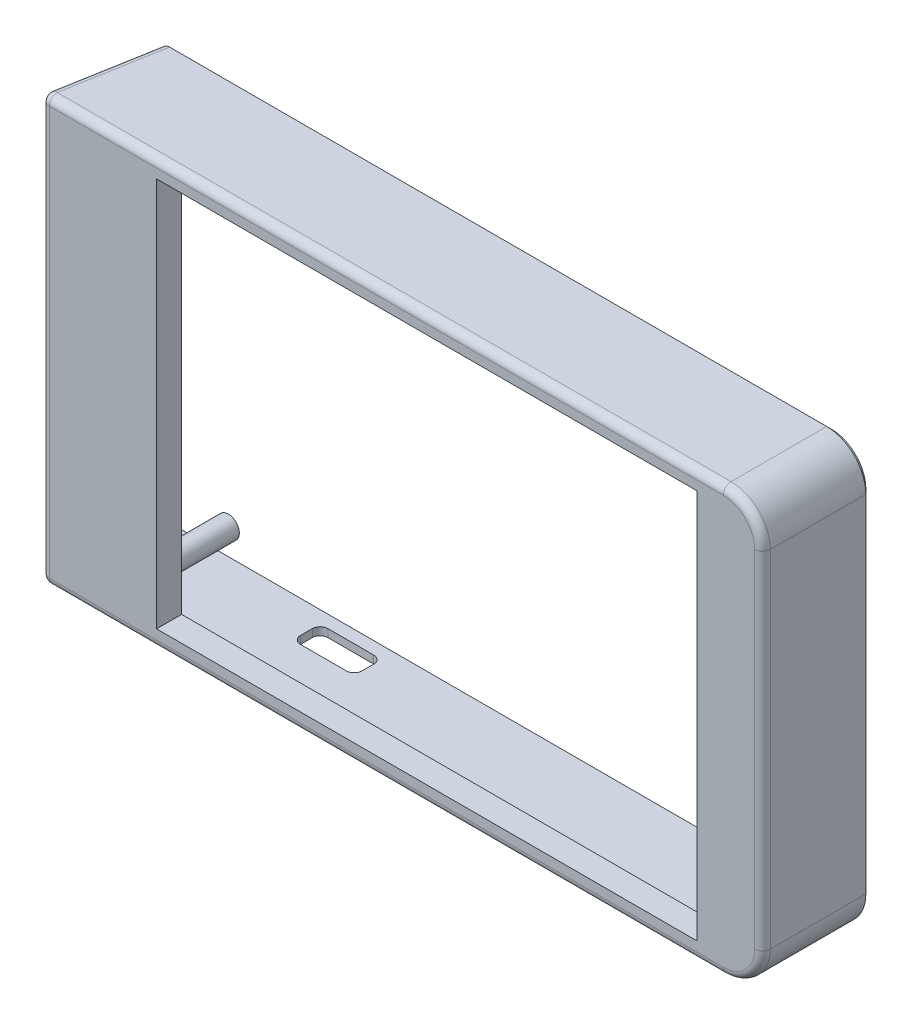
SolidWorks part; units mm, degrees
ref_plane "Front Plane" through (0, 0, 0) normal (0, 0, 1) x (1, 0, 0)
ref_plane "Top Plane" through (0, 0, 0) normal (0, 1, 0) x (1, 0, 0)
ref_plane "Right Plane" through (0, 0, 0) normal (1, 0, 0) x (0, 0, -1)
sketch "Sketch1" plane through (0, 0, 0) normal (0, 0, 1) x (1, 0, 0)
  line L0 (-39.8484, 30.2167) -> (-39.8484, 39.4369) construction
  line L1 (-52.5926, -12.5567) -> (37.3102, -12.5567)
  line L2 (-52.5926, -12.5567) -> (-52.5926, 41.6369)
  line L3 (-52.5926, 41.6369) -> (37.3102, 41.6369)
  line L4 (37.3102, -12.5567) -> (37.3102, 41.6369)
  line L5 (-40.0484, 39.6369) -> (29.1634, 39.6369)
  line L6 (-40.0484, 39.6369) -> (-40.0484, -10.5249)
  line L7 (-40.0484, -10.5249) -> (29.1634, -10.5249)
  line L8 (29.1634, 39.6369) -> (29.1634, -10.5249)
  line L9 (-39.8484, 39.4369) -> (29.1634, 39.4369) construction
  line L10 (29.1634, 39.4369) -> (29.1634, -10.5249) construction
  line L11 (29.1634, -10.5249) -> (-39.8484, -10.5249) construction
  line L13 (35.3102, -10.5567) -> (-50.5926, -10.5567) construction
  line L14 (-50.5926, -10.5567) -> (-50.5926, 39.5829) construction
  line L15 (35.3102, 39.5829) -> (35.3102, -10.5567) construction
  dimension "D1" = 2
  dimension "D2" = 2
  dimension "D3" = 0.2
  dimension "D4" = 0.2
  dimension "D5" = 0
  dimension "D6" = 0
  dimension "D7" = 2
  dimension "D8" = 2
extrude "Boss-Extrude1" add sketch "Sketch1" along normal blind 3.2
sketch "Sketch2" plane through (0, 0, 0) normal (0, 0, -1) x (-1, 0, 0)
  line L0 (49.6782, 29.2768) -> (49.6782, 27.6893) construction
  line L1 (50.6782, 33.2931) -> (46.1987, 33.2931)
  line L2 (50.6782, 33.2931) -> (50.6782, -2.2669)
  line L3 (50.6782, -2.2669) -> (46.1987, -2.2669)
  line L4 (46.1987, 33.2931) -> (46.1987, -2.2669)
  line L5 (47.1987, 31.9912) -> (47.1987, -2.9651) construction
  line L6 (47.6145, 32.2931) -> (49.202, 32.2931) construction
  line L7 (49.202, -3.2669) -> (47.6145, -3.2669) construction
  dimension "D1" = 1
  dimension "D2" = 1
  dimension "D3" = 1
  dimension "D4" = 1
extrude "Cut-Extrude1" cut sketch "Sketch2" against normal blind 2
sketch "Sketch3" plane through (0, 0, 0) normal (0, 0, -1) x (-1, 0, 0)
  line L1 (-37.3102, 41.6369) -> (52.5926, 41.6369)
  line L2 (-37.3102, 41.6369) -> (-37.3102, -12.5567)
  line L3 (-37.3102, -12.5567) -> (52.5926, -12.5567)
  line L4 (52.5926, 41.6369) -> (52.5926, -12.5567)
  line L5 (-36.3102, 40.6369) -> (51.5926, 40.6369)
  line L6 (-36.3102, 40.6369) -> (-36.3102, -11.5567)
  line L7 (-36.3102, -11.5567) -> (51.5926, -11.5567)
  line L8 (51.5926, 40.6369) -> (51.5926, -11.5567)
  dimension "D1" = 1
  dimension "D2" = 1
  dimension "D3" = 1
  dimension "D4" = 1
extrude "Boss-Extrude2" add sketch "Sketch3" along normal blind 10
sketch "Sketch4" plane through (0, 0, 0) normal (0, 0, -1) x (-1, 0, 0)
  line L0 (-35.3102, 14.5131) -> (49.6764, 14.5131) construction
  line L1 (-35.3102, 39.5829) -> (-35.3102, -10.5567) construction
  line L2 (49.6764, -2.9651) -> (49.6764, 31.9912) construction
  circle A0 centre (-32.2241, -7.4452) radius 1.4
  circle A2 centre (-32.2241, 36.4714) radius 1.4
  circle A3 centre (43.8743, -7.4452) radius 1.4
  circle A4 centre (43.8743, 36.4714) radius 1.4
  dimension "D1" = 2.8
extrude "Boss-Extrude3" add sketch "Sketch4" along normal offset from surface (9.8 mm away) 0.2
sketch "Sketch5" plane through (0, -12.5567, 0) normal (0, -1, 0) x (1, 0, 0)
  line L0 (-31.1676, -6) -> (-31.1676, -8.5) construction
  line L1 (-31.3676, -9) -> (-23.5176, -9)
  line L2 (-31.3676, -9) -> (-31.3676, -5.5)
  line L3 (-31.3676, -5.5) -> (-23.5176, -5.5)
  line L4 (-23.5176, -9) -> (-23.5176, -5.5)
  line L5 (-23.7176, -6) -> (-23.7176, -8.5) construction
  line L6 (-31.1676, -6) -> (-23.7176, -6) construction
  line L7 (-31.1676, -8.5) -> (-23.7176, -8.5) construction
  dimension "D1" = 0.2
  dimension "D2" = 0.2
  dimension "D3" = 0.5
  dimension "D4" = 0.5
extrude "Cut-Extrude2" cut sketch "Sketch5" against normal up to surface (1 mm away) up to face at (-7.6412, -11.5567, -5)
sketch "Sketch6" plane through (0, -12.5567, 0) normal (0, -1, 0) x (-1, 0, 0)
  line L0 (52.5926, 10) -> (54.9201, -3.2)
  line L1 (54.9201, -3.2) -> (52.5926, -3.2)
  line L2 (52.5926, -3.2) -> (52.5926, 10)
  line L3 (52.5926, -3.2) -> (-37.3102, -3.2) construction
  dimension "D1" = 80
extrude "Boss-Extrude4" add sketch "Sketch6" against normal up to surface (54.1936 mm away) up to face at (-7.6412, 41.6369, -3.4)
fillet "Fillet1" radius 4 2 edges at (36.3102, 40.6369, -5) (36.3102, -11.5567, -5)
fillet "Fillet2" radius 5 2 edges at (37.3102, -12.5567, -3.4) (37.3102, 41.6369, -3.4)
fillet "Fillet3" radius 1 5 edges at (-11.305, -12.5567, 3.2) (35.8457, -11.0923, 3.2) (37.3102, 14.5401, 3.2) (35.8457, 40.1724, 3.2) (-11.305, 41.6369, 3.2)
sketch "Sketch7" plane through (0, 0, -9.8) normal (0, 0, -1) x (-1, 0, 0)
  circle A0 centre (-32.2241, -7.4452) radius 0.7
  circle A1 centre (-32.2241, 36.4714) radius 0.7
  circle A2 centre (43.8743, 36.4714) radius 0.7
  circle A3 centre (43.8743, -7.4452) radius 0.7
  dimension "D1" = 1.4
extrude "Cut-Extrude3" cut sketch "Sketch7" against normal blind 6
fillet "Fillet4" radius 1 5 edges at (-53.6682, -12.5567, -3.9) (-54.8685, -12.2638, 2.9071) (-54.9201, 14.5401, 3.2) (-54.8685, 41.344, 2.9071) (-53.6682, 41.6369, -3.9)
fillet "Fillet5" radius 1 4 edges at (-31.3676, -12.0567, -5.5) (-31.3676, -12.0567, -9) (-23.5176, -12.0567, -9) (-23.5176, -12.0567, -5.5)
sketch "Sketch9" plane through (0, 0, -10) normal (0, 0, -1) x (-1, 0, 0)
  line L0 (-32.3102, 40.6369) -> (51.5926, 40.6369)
  line L1 (51.5926, 40.6369) -> (51.5926, -11.5567)
  line L2 (51.5926, -11.5567) -> (-32.3102, -11.5567)
  line L3 (-36.3102, 36.6369) -> (-36.3102, -7.5567)
  line L4 (51.9926, 41.0369) -> (-32.3102, 41.0369)
  line L5 (-36.7102, 36.6369) -> (-36.7102, -7.5567)
  line L6 (-32.3102, -11.9567) -> (51.9926, -11.9567)
  line L7 (51.9926, -11.9567) -> (51.9926, 41.0369)
  arc A0 (-36.3102, 36.6369) -> (-32.3102, 40.6369) centre (-32.3102, 36.6369) cw
  arc A1 (-36.3102, -7.5567) -> (-32.3102, -11.5567) centre (-32.3102, -7.5567) ccw
  arc A2 (-36.3102, -7.5567) -> (-32.3102, -11.5567) centre (-32.3102, -7.5567) ccw construction
  arc A3 (-32.3102, 40.6369) -> (-36.3102, 36.6369) centre (-32.3102, 36.6369) ccw construction
  arc A4 (-36.7102, 36.6369) -> (-32.3102, 41.0369) centre (-32.3102, 36.6369) cw
  arc A5 (-36.7102, -7.5567) -> (-32.3102, -11.9567) centre (-32.3102, -7.5567) ccw
  point P28 (-36.7102, -6.2766)
  dimension "D1" = 0.4
  dimension "D2" = 0.4
  dimension "D3" = 0.4
  dimension "D4" = 0.4
extrude "Boss-Extrude6" add sketch "Sketch9" along normal blind 0.6
fillet "Fillet6" radius 0.4 2 edges at (-51.9926, 41.0369, -10.3) (-51.9926, -11.9567, -10.3)
sketch "Sketch10" plane through (0, 0, 3.2) normal (0, 0, 1) x (1, 0, 0)
  line L0 (-40.0484, -10.3249) -> (-40.0484, -10.5249)
  line L1 (-40.0484, 39.6369) -> (29.1634, 39.6369)
  line L2 (-40.0484, 39.6369) -> (-40.0484, 39.4369)
  line L3 (-40.0484, -10.5249) -> (29.1634, -10.5249)
  line L4 (29.1634, 39.6369) -> (29.1634, -10.5249)
  line L5 (-40.0484, 39.4369) -> (28.9634, 39.4369)
  line L7 (-40.0484, -10.3249) -> (28.9634, -10.3249)
  line L8 (28.9634, 39.4369) -> (28.9634, -10.3249)
  point P10 (-38.7609, -10.5249)
  point P11 (0, 0)
  dimension "D1" = 0.2
  dimension "D2" = 0.2
  dimension "D3" = 0.2
extrude "Boss-Extrude7" add sketch "Sketch10" against normal up to surface (3.2 mm away) up to face at (-42.4743, 36.4714, 0)
